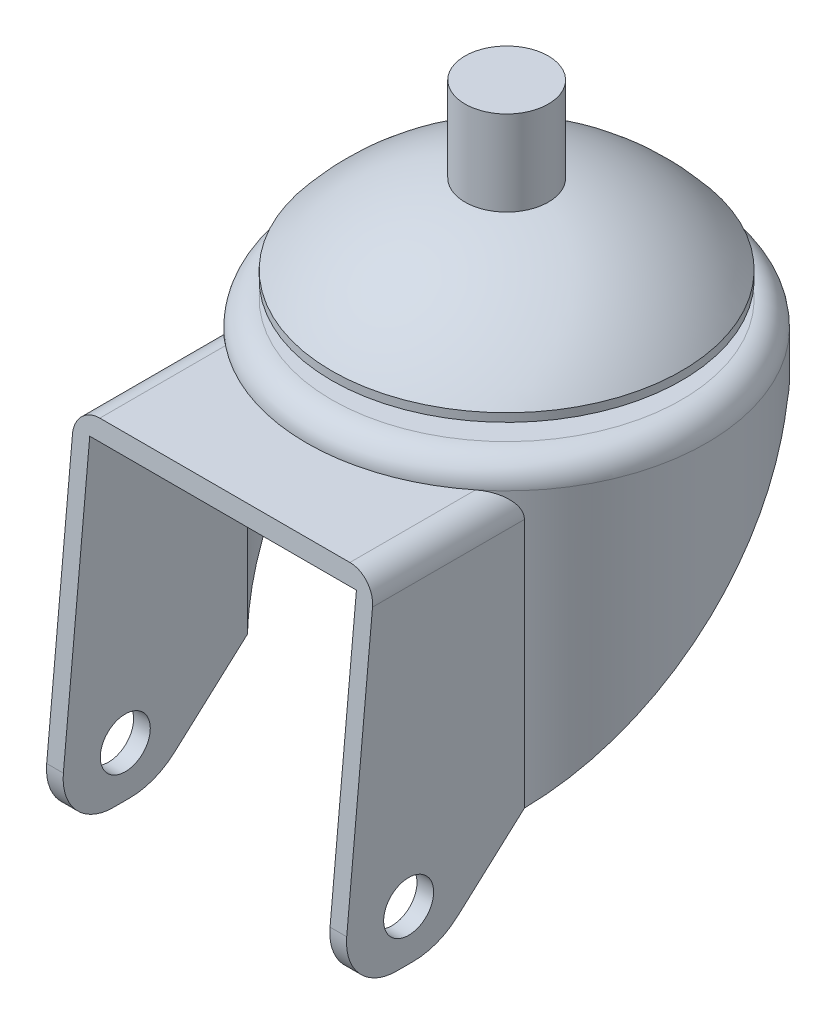
SolidWorks part; units mm, degrees
ref_plane "Front Plane" through (0, 0, 0) normal (0, 0, 1) x (1, 0, 0)
ref_plane "Top Plane" through (0, 0, 0) normal (0, 1, 0) x (1, 0, 0)
ref_plane "Right Plane" through (0, 0, 0) normal (1, 0, 0) x (0, 0, -1)
sketch "Sketch1" plane through (0, 0, 0) normal (0, 1, 0) x (1, 0, 0)
  circle A0 centre (0, 0) radius 24
  dimension "D1" = 48
extrude "Boss-Extrude1" add sketch "Sketch1" along normal blind 42
fillet "Fillet1" radius 3 1 edges at (0, 42, 24)
sketch "Sketch2" plane through (0, 0, 0) normal (1, 0, 0) x (0, 0, -1)
  line L0 (-24, 39) -> (-33.8137, 39)
  line L1 (-33.8137, 39) -> (-37.8162, -3.269)
  line L2 (-37.8162, -3.269) -> (-26.1566, -3.269)
  line L3 (24, 34.6682) -> (15.9572, 34.6682)
  line L4 (24, 0) -> (24, 39) construction
  line L5 (15.9572, 34.6682) -> (-26.1566, -3.269)
  line L6 (-24, 39) -> (24, 39)
  line L7 (24, 39) -> (24, 34.6682)
extrude "Boss-Extrude2" add sketch "Sketch2" along normal blind 18 and the other way blind 18
sketch "Sketch4" plane through (0, 0, 0) normal (0, -1, 0) x (1, 0, 0)
  line L1 (8.2766, 22.5277) -> (-8.2766, 22.5277)
  line L2 (8.2766, 22.5277) -> (-8.2766, 22.5277)
  line L3 (-22.1651, -9.2036) -> (23.0026, -9.2036)
  line L4 (-22.1651, -9.2036) -> (-22.1651, -25.0955)
  line L5 (-22.1651, -25.0955) -> (23.0026, -25.0955)
  line L6 (23.0026, -9.2036) -> (23.0026, -25.0955)
  arc A1 (-8.2766, 22.5277) -> (8.2766, 22.5277) centre (0, 0) ccw
  arc A2 (-8.2766, 22.5277) -> (8.2766, 22.5277) centre (0, 0) ccw
  arc M3 (-8.2766, 22.5277) -> (8.2766, 22.5277) centre (0, 0) ccw
  dimension "D1" = 0
extrude "Cut-Extrude2" cut sketch "Sketch4" against normal blind 42 contours L6 L3 L4 L5 M3 region at (22.5839, 0, -9.6824)
sketch "Sketch5" plane through (0, 0, 0) normal (1, 0, 0) x (0, 0, -1)
  line L0 (-26.1566, -3.269) -> (14.622, 33.5)
  line L1 (14.622, 33.5) -> (25.7819, 33.5)
  line L2 (25.7819, 33.5) -> (25.7819, -3.269)
  line L3 (25.7819, -3.269) -> (-26.1566, -3.269)
  dimension "D1" = 8.5
extrude "Cut-Extrude3" cut sketch "Sketch5" against normal through all and the other way through all
fillet "Fillet2" radius 6 1 edges at (0, -3.269, 37.8162)
fillet "Fillet3" radius 8 1 edges at (0, -3.269, 26.1566)
fillet "Fillet4" radius 3 2 edges at (-18, 39, 24.8441) (18, 39, 24.8441)
sketch "Sketch6" plane through (0, -3.269, 0) normal (0, -1, 0) x (1, 0, 0)
  line L0 (18, 37.2212) -> (-18, 37.2212) construction
  line L1 (-16, 72.1642) -> (16, 72.1642)
  line L2 (-16, 72.1642) -> (-16, 2.2782)
  line L3 (-16, 2.2782) -> (16, 2.2782)
  line L4 (16, 72.1642) -> (16, 2.2782)
  line L5 (-16, 72.1642) -> (16, 2.2782) construction
  line L6 (-16, 2.2782) -> (16, 72.1642) construction
  line L7 (18, 31.2212) -> (18, 29.2307) construction
  circle A0 centre (0, 0) radius 22
  arc A1 (19.0315, -14.622) -> (18, 15.8745) centre (0, 0) ccw construction
  point P6 (0, 37.2212)
  line M2 (-18, 29.2307) -> (18, 29.2307)
  line M4 (18, 31.2212) -> (-18, 31.2212)
  dimension "D1" = 2
  dimension "D2" = 2
extrude "Cut-Extrude5" cut sketch "Sketch6" against normal blind 40 contours L2 A0 L4 L3 | L4 A0 L2 L3 | L4 L2 M4 M2 | L4 L1 L2 M4 | A0 L4 L2 M2 region at (0, -3.269, 51.6927) region at (0, -3.269, 30.226) region at (0, -3.269, 24.3362) region at (0, -3.269, 11.1856) region at (0, -3.269, -6.5737)
sketch "Sketch7" plane through (0, 36.731, 0) normal (0, -1, 0) x (1, 0, 0)
  circle A0 centre (0, 0) radius 16
  dimension "D1" = 32
extrude "Boss-Extrude3" add sketch "Sketch7" along normal blind 1
sketch "Sketch8" plane through (0, 35.731, 0) normal (0, -1, 0) x (1, 0, 0)
  circle A0 centre (0, 0) radius 10
  dimension "D1" = 20
extrude "Cut-Extrude6" cut sketch "Sketch8" against normal blind 3
chamfer "Chamfer1" distance 3 angle 45 1 edges at (0, 38.731, -10)
sketch "Sketch9" plane through (0, 38.731, 0) normal (0, -1, 0) x (1, 0, 0)
  circle A0 centre (0, 0) radius 5
  dimension "D1" = 10
extrude "Boss-Extrude4" add sketch "Sketch9" along normal blind 4
chamfer "Chamfer2" distance 1 angle 45 1 edges at (0, 34.731, -5)
sketch "Sketch10" plane through (18, 0, 0) normal (1, 0, 0) x (0, 0, -1)
  line L0 (-31.2212, -3.269) -> (-29.2307, -3.269) construction
  circle A0 centre (-29.7632, 2.731) radius 3
  circle A1 centre (-29.7632, 2.731) radius 31.75 construction
  dimension "D1" = 6
  dimension "D2" = 63.5
  dimension "D3" = 6
extrude "Cut-Extrude7" cut sketch "Sketch10" against normal through all
sketch "Sketch11" plane through (0, 42, 0) normal (0, 1, 0) x (1, 0, 0)
  circle A0 centre (0, 0) radius 7.5
  dimension "D1" = 15
extrude "Boss-Extrude5" add sketch "Sketch11" along normal blind 2
sketch "Sketch12" plane through (0, 44, 0) normal (0, 1, 0) x (1, 0, 0)
  circle A0 centre (0, 0) radius 21
  dimension "D1" = 42
extrude "Boss-Extrude6" add sketch "Sketch12" along normal blind 1
dome "Dome1" faces to dome 1 distance 10 reverse direction no elliptical dome no face at (0, 45, 21) parameters "D1"=10
sketch "Sketch13" plane through (0, 34.731, 0) normal (0, -1, 0) x (1, 0, 0)
  circle A0 centre (0, 0) radius 5
extrude "Boss-Extrude7" add sketch "Sketch13" against normal blind 30
scale "Scale1" scale about centroid uniform scaling yes scale factor 0.7761
